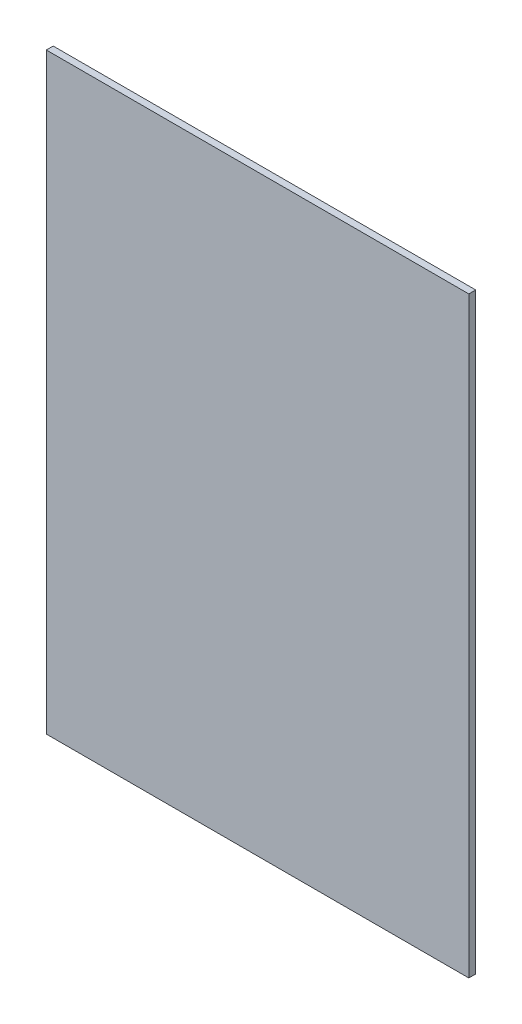
SolidWorks part; units mm, degrees
ref_plane "Front Plane" through (0, 0, 0) normal (0, 0, 1) x (1, 0, 0)
ref_plane "Top Plane" through (0, 0, 0) normal (0, 1, 0) x (1, 0, 0)
ref_plane "Right Plane" through (0, 0, 0) normal (1, 0, 0) x (0, 0, -1)
sketch "Sketch1" plane through (0, 0, 0) normal (0, 0, 1) x (1, 0, 0)
  line L1 (0, 0) -> (184, 0)
  line L2 (0, 0) -> (0, 258)
  line L3 (0, 258) -> (184, 258)
  line L4 (184, 0) -> (184, 258)
  dimension "D1" = 184
  dimension "D2" = 258
extrude "Boss-Extrude1" add sketch "Sketch1" along normal blind 3
